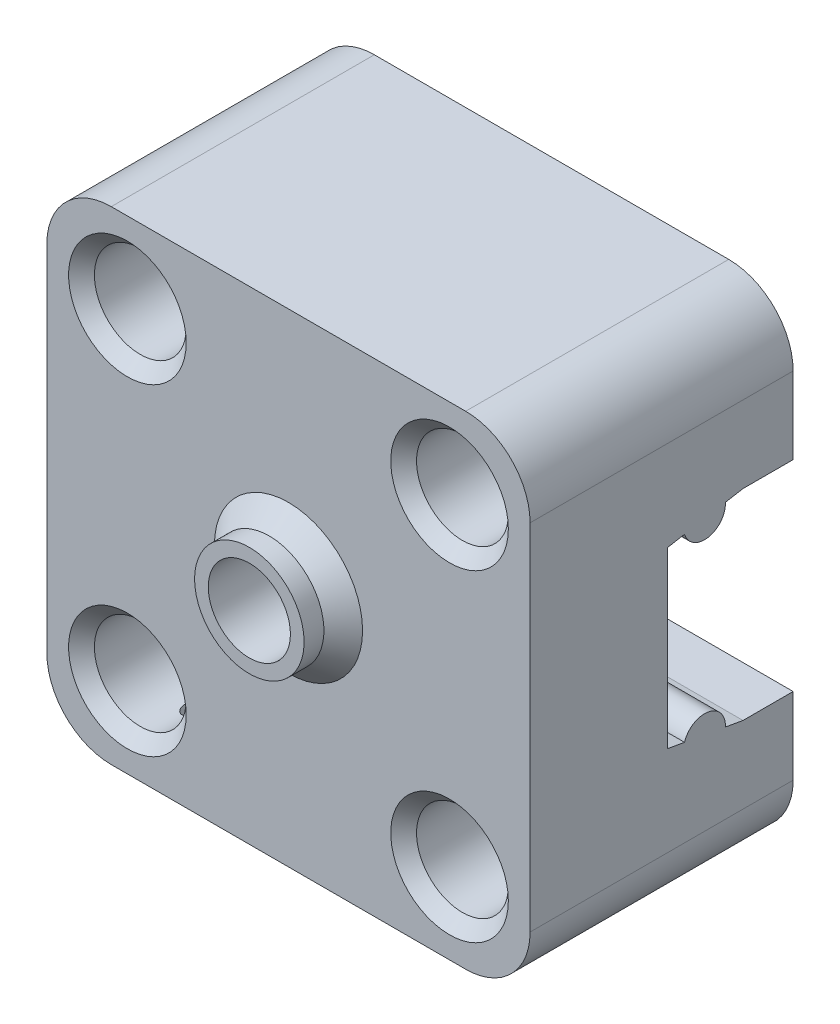
SolidWorks part; units mm, degrees
note: The reader was unsure of these and kept them because the rebuilt part matched: shared geometry of "Sketch1<3>".
ref_plane "Front Plane" through (0, 0, 0) normal (0, 0, 1) x (1, 0, 0)
ref_plane "Top Plane" through (0, 0, 0) normal (0, 1, 0) x (1, 0, 0)
ref_plane "Right Plane" through (0, 0, 0) normal (1, 0, 0) x (0, 0, -1)
sketch "Sketch1" plane through (0, 0, 0) normal (0, 0, 1) x (1, 0, 0)
  line L0 (10, 20) -> (10, 0) construction
  line L1 (0, 0) -> (20, 0) construction
  line L2 (0, 0) -> (0, 20) construction
  line L3 (0, 20) -> (20, 20) construction
  line L4 (20, 0) -> (20, 20) construction
  line L5 (10, 10) -> (68.0208, 10) construction
  line L6 (-5, -5) -> (25, -5)
  line L7 (-5, -5) -> (-5, 25)
  line L8 (-5, 25) -> (25, 25)
  line L9 (25, -5) -> (25, 25)
  line L10 (-5, -5) -> (25, 25) construction
  line L11 (-5, 25) -> (25, -5) construction
  line L13 (25, 16) -> (95, 16)
  line L14 (25, 16) -> (25, 4)
  line L15 (25, 4) -> (95, 4)
  line L16 (95, 16) -> (95, 4)
  circle A0 centre (0, 0) radius 1.6
  circle A1 centre (0, 20) radius 1.6
  circle A2 centre (20, 20) radius 1.6
  circle A3 centre (20, 0) radius 1.6
  point P11 (10, 10)
  dimension "D2" = 3.2
  dimension "D1" = 20
  dimension "D3" = 30
  dimension "D4" = 30
  dimension "D5" = 12
  dimension "D6" = 6
  dimension "D7" = 70
extrude "Boss-Extrude1" add sketch "Sketch1" along normal blind 6 contours L6 L9 L8 L7 A3 A2 A1 A0 | L16 L13 L9 L15
extrude "Boss-Extrude2" add sketch "Sketch1<3>" along normal blind 22.33 contours L6 L9 L8 L7 A3 A2 A1 A0
sketch "Sketch1<3>" plane through (0, 0, 0) normal (0, 0, 1) x (1, 0, 0) same geometry as "Sketch1"
sketch "Sketch2" plane through (25, 0, 0) normal (1, 0, 0) x (0, 0, -1)
  line L0 (-6.5155, 16.2317) -> (-9.1122, 16.2317)
  line L1 (-9.1122, 16.2317) -> (-10.2045, 16.0391)
  line L2 (-12.7425, 15.5915) -> (-13.7862, 15.4075)
  line L3 (-13.7862, 15.4075) -> (-13.7862, 4.5918)
  line L4 (-13.7862, 4.5918) -> (-12.7425, 4.4077)
  line L5 (-10.2045, 3.9602) -> (-9.1122, 3.7676)
  line L6 (-9.1122, 3.7676) -> (-6.5155, 3.7676)
  line L7 (-6.5155, 3.7676) -> (-5.9025, 3.7676)
  line L9 (-5.9025, 16.2317) -> (-6.5155, 16.2317)
  line L11 (-22.33, -5) -> (0, -5) construction
  line L12 (-22.33, -5) -> (-22.33, 25) construction
  line L13 (-5.9025, 16.2317) -> (-5.9025, 3.7676)
  arc A0 (-12.7425, 15.5915) -> (-10.2045, 16.0391) centre (-11.5011, 15.972) ccw
  arc A1 (-10.2045, 3.9602) -> (-12.7425, 4.4077) centre (-11.5011, 4.0273) ccw
extrude "Cut-Extrude1" cut sketch "Sketch2" against normal through all
sketch "Sketch3" plane through (0, 0, 22.33) normal (0, 0, 1) x (1, 0, 0)
  line L0 (-5, 10) -> (25, 10) construction
  line L1 (-5, -5) -> (-5, 25) construction
  line L2 (25, -5) -> (25, 25) construction
  line L3 (10, -5) -> (10, 25) construction
  line L4 (-5, -5) -> (25, -5) construction
  line L5 (-5, 25) -> (25, 25) construction
  circle A0 centre (10, 10) radius 2.55
  dimension "D1" = 5.1
extrude "Cut-Extrude2" cut sketch "Sketch3" against normal blind 8
sketch "Sketch5" plane through (0, 0, 13.7862) normal (0, 0, -1) x (-1, 0, 0)
  line L1 (-5.3235, 10) -> (-7.6617, 14.05)
  line L2 (-7.6617, 14.05) -> (-12.3383, 14.05)
  line L3 (-12.3383, 14.05) -> (-14.6765, 10)
  line L4 (-14.6765, 10) -> (-12.3383, 5.95)
  line L5 (-12.3383, 5.95) -> (-7.6617, 5.95)
  line L6 (-7.6617, 5.95) -> (-5.3235, 10)
  line L8 (-25, 15.4075) -> (-25, 4.5918)
  line L9 (-25, 4.5918) -> (5, 4.5918)
  line L10 (5, 4.5918) -> (5, 15.4075)
  line L11 (5, 15.4075) -> (-25, 15.4075)
  line L12 (-25, 15.4075) -> (-25, 4.5918)
  line L13 (-25, 4.5918) -> (5, 4.5918)
  line L15 (5, 15.4075) -> (-25, 15.4075)
  line L18 (5, 4.5918) -> (5, 15.4075)
  circle A0 centre (-10, 10) radius 4.05
  circle A1 centre (-10, 10) radius 4.05 construction
  dimension "D2" = 8.1
  dimension "D3" = 8.1
  dimension "D1" = 0
extrude "Cut-Extrude3" cut sketch "Sketch5" against normal blind 4.5
sketch "Sketch6" plane through (0, 0, 0) normal (0, 0, -1) x (-1, 0, 0)
  line L0 (-20, 0) -> (0, 20) construction
  line L1 (0, 20) -> (0, 0) construction
  line L2 (0, 0) -> (-20, 20) construction
  circle A0 centre (-10, 10) radius 5
  dimension "D1" = 10
extrude "Cut-Extrude5" cut sketch "Sketch6" against normal blind 8.6
sketch "Sketch7" plane through (0, 0, 0) normal (0, 0, -1) x (-1, 0, 0)
  line L1 (5, -5) -> (-3.5, -5)
  line L2 (5, -5) -> (5, 25)
  line L3 (5, 25) -> (-3.5, 25)
  line L4 (-3.5, -5) -> (-3.5, 25)
  line L5 (5, 25) -> (-25, 25) construction
  line L6 (-95, 10) -> (-3.5, 10) construction
  line L7 (-95, 16) -> (-95, 4) construction
  line L8 (-3.5, 10) -> (-3.5, 16)
  line L9 (-25, 4) -> (-95, 4) construction
  line L10 (-3.5, 16) -> (-65, 16)
  line L11 (-3.5, 16) -> (-3.5, 4)
  line L12 (-3.5, 4) -> (-65, 4)
  line L13 (-65, 16) -> (-65, 4)
  circle A0 centre (-38.5, 10) radius 1.6
  circle A1 centre (-63.5, 10) radius 1.6
  circle A2 centre (-88.5, 10) radius 1.6
  dimension "D4" = 35
  dimension "D5" = 60
  dimension "D6" = 3.2
  dimension "D7" = 3.2
  dimension "D1" = 30
  dimension "D2" = 8.5
  dimension "D3" = 6
  dimension "D8" = 25
extrude "Cut-Extrude6" cut sketch "Sketch7" against normal through all contours L6 A2 | A2 L6 | A1 | A0
sketch "Sketch8" plane through (0, 0, 22.33) normal (0, 0, 1) x (1, 0, 0)
  circle A0 centre (20, 20) radius 2.85
  circle A1 centre (20, 0) radius 2.85
  circle A2 centre (0, 0) radius 2.85
  circle A3 centre (0, 20) radius 2.85
  dimension "D4" = 5.7
extrude "Cut-Extrude7" cut sketch "Sketch8" against normal blind 11
sketch "Sketch9" plane through (0, 0, 22.33) normal (0, 0, 1) x (1, 0, 0)
  circle A0 centre (10, 10) radius 2.55
  circle A1 centre (10, 10) radius 3.4
  dimension "D1" = 5.1
  dimension "D2" = 6.8
extrude "Boss-Extrude3" add sketch "Sketch9" along normal blind 2.43
chamfer "Chamfer1" distance 1.2 angle 45 1 edges at (13.4, 10, 22.33)
fillet "Fillet3" radius 4 8 edges at (25, 4, 2.9513) (25, 16, 2.9513) (25, 25, 11.165) (-5, 25, 11.165) (-5, -5, 11.165) (25, -5, 11.165) (95, 4, 3) (95, 16, 3)
chamfer "Chamfer2" distance 0.8 angle 45 4 edges at (22.85, 0, 22.33) (2.85, 0, 22.33) (2.85, 20, 22.33) (22.85, 20, 22.33)
sketch "Sketch10" plane through (0, 0, 0) normal (0, 0, -1) x (-1, 0, 0)
  line L1 (-85.2668, 10) -> (-86.8834, 12.8)
  line L2 (-86.8834, 12.8) -> (-90.1166, 12.8)
  line L3 (-90.1166, 12.8) -> (-91.7332, 10)
  line L4 (-91.7332, 10) -> (-90.1166, 7.2)
  line L5 (-90.1166, 7.2) -> (-86.8834, 7.2)
  line L6 (-86.8834, 7.2) -> (-85.2668, 10)
  circle A3 centre (-88.5, 10) radius 2.8 construction
  dimension "D1" = 5.6
extrude "Cut-Extrude8" cut sketch "Sketch10" against normal blind 3
chamfer "Chamfer3" distance 0.8 angle 45 6 edges at (86.0751, 8.6, 0) (88.5, 7.2, 0) (90.9249, 8.6, 0) (90.9249, 11.4, 0) (86.0751, 11.4, 0) (88.5, 12.8, 0)
pattern_linear "LPattern1" count 3 spacing 25 along (-1, 0, 0) of "Chamfer3", "Cut-Extrude8"
sketch "Sketch12" plane through (0, 0, 0) normal (0, 0, -1) x (-1, 0, 0)
  line L1 (6.555, -7.0675) -> (-96.6557, -7.0675)
  line L2 (6.555, -7.0675) -> (6.555, 26.7654)
  line L3 (6.555, 26.7654) -> (-96.6557, 26.7654)
  line L4 (-96.6557, -7.0675) -> (-96.6557, 26.7654)
extrude "Cut-Extrude9" cut sketch "Sketch12" against normal blind 6
sketch "Sketch13" plane through (0, -5, 0) normal (0, -1, 0) x (1, 0, 0)
  line L0 (-1, 22.33) -> (-1, 6) construction
  circle A0 centre (1, 18.9498) radius 0.8
  circle A1 centre (1, 12.4498) radius 0.8
  dimension "D1" = 1.6
  dimension "D2" = 1.6
  dimension "D3" = 6.5
  dimension "D4" = 2
extrude "Cut-Extrude10" cut sketch "Sketch13" against normal blind 5
